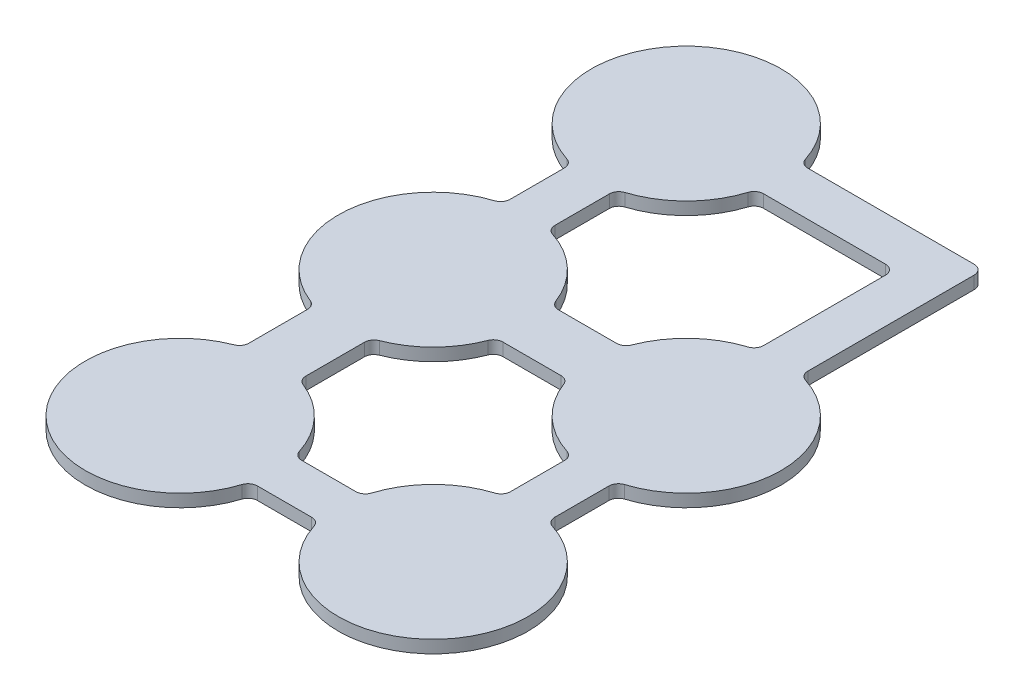
SolidWorks part; units mm, degrees
ref_plane "Front Plane" through (0, 0, 0) normal (0, 0, 1) x (1, 0, 0)
ref_plane "Top Plane" through (0, 0, 0) normal (0, 1, 0) x (1, 0, 0)
ref_plane "Right Plane" through (0, 0, 0) normal (1, 0, 0) x (0, 0, -1)
sketch "Sketch1" plane through (0, 0, 0) normal (0, 1, 0) x (1, 0, 0)
  line L0 (-10, 0) -> (10, 0) construction
  line L1 (-10, 0) -> (-10, 20) construction
  line L2 (-10, 0) -> (-10, -20) construction
  line L3 (-10, -20) -> (10, -20) construction
  line L4 (10, -20) -> (10, 0) construction
  line L6 (-11.775, 12.7131) -> (-8.225, 12.7131)
  line L7 (-11.775, 12.7131) -> (-11.775, 7.2869)
  line L8 (-11.775, 7.2869) -> (-8.225, 7.2869)
  line L9 (-8.225, 12.7131) -> (-8.225, 7.2869)
  line L14 (-12.25, -7.1545) -> (-7.75, -7.1545)
  line L15 (-12.25, -7.1545) -> (-12.25, -12.8455)
  line L16 (-12.25, -12.8455) -> (-7.75, -12.8455)
  line L17 (-7.75, -7.1545) -> (-7.75, -12.8455)
  line L18 (-2.707, -18.25) -> (2.707, -18.25)
  line L19 (-2.707, -18.25) -> (-2.707, -21.75)
  line L20 (-2.707, -21.75) -> (2.707, -21.75)
  line L21 (2.707, -18.25) -> (2.707, -21.75)
  line L22 (8.25, -7.293) -> (11.75, -7.293)
  line L23 (8.25, -7.293) -> (8.25, -12.707)
  line L24 (8.25, -12.707) -> (11.75, -12.707)
  line L25 (11.75, -7.293) -> (11.75, -12.707)
  line L26 (-2.8299, 2.2) -> (2.8299, 2.2)
  line L27 (-2.8299, 2.2) -> (-2.8299, -2.2)
  line L28 (-2.8299, -2.2) -> (2.8299, -2.2)
  line L29 (2.8299, 2.2) -> (2.8299, -2.2)
  line L30 (-2.707, 21.75) -> (11.75, 21.75)
  line L31 (-2.707, 21.75) -> (-2.707, 18.25)
  line L32 (-2.707, 18.25) -> (11.75, 18.25)
  line L33 (11.75, 21.75) -> (11.75, 18.25)
  line L34 (11.75, 7.293) -> (8.25, 7.293)
  line L35 (11.75, 7.293) -> (11.75, 21.75)
  line L36 (11.75, 21.75) -> (8.25, 21.75)
  line L37 (8.25, 7.293) -> (8.25, 21.75)
  circle A0 centre (10, 0) radius 7.5
  circle A1 centre (-10, 0) radius 7.5
  circle A2 centre (-10, 20) radius 7.5
  circle A3 centre (-10, -20) radius 7.5
  circle A4 centre (10, -20) radius 7.5
  point P10 (0, 0)
  point P15 (-10, 12.7131)
  point P33 (-10, -7.1545)
  point P34 (-2.707, -20)
  point P35 (10, -7.293)
  point P36 (-2.8299, 0)
  point P44 (6.0643, 7.5)
  point P45 (0, 0)
  point P46 (0, 0)
  point P47 (0, 0)
  point P48 (0, 0)
  point P49 (0, 0)
  dimension "D1" = 15
  dimension "D2" = 20
  dimension "D3" = 3.55
  dimension "D4" = 4.5
  dimension "D5" = 4.4
  dimension "D6" = 3.5
  dimension "D7" = 3.5
  dimension "D8" = 3.5
extrude "Boss-Extrude1" add sketch "Sketch1" along normal blind 1 contours A3 L17 A1 L15 | A4 L18 A3 L20 | A4 L25 A0 L23 | A0 L35 L32 L37 | A1 L28 A0 L26 | L37 L32 L33 L30 | A2 L32 L37 L30 | A2 L7 A1 L9 | A1 | A3 | A4 | A0 | A2 region at (-10, 0, -10) region at (2.8405, 0, -20) region at (-10, 0, 10) region at (10, 0, -20) region at (0, 0, 0) region at (10, 0, -12.8405) region at (0, 0, 20) region at (10, 0, 10)
fillet "Fillet1" radius 0.75 26 edges at (2.8299, 0.5, -2.2) (-2.8299, 0.5, -2.2) (11.75, 0.5, -21.75) (-2.707, 0.5, -21.75) (8.25, 0.5, -7.293) (11.75, 0.5, -7.293) (11.75, 0.5, 12.707) (2.707, 0.5, 21.75) (-2.707, 0.5, 21.75) (-2.707, 0.5, 18.25) (2.707, 0.5, 18.25) (8.25, 0.5, 12.707) (11.75, 0.5, 7.293) (-2.8299, 0.5, 2.2) (2.8299, 0.5, 2.2) (8.25, 0.5, 7.293) (-12.25, 0.5, 12.8455) (-7.75, 0.5, 12.8455) (-7.75, 0.5, 7.1545) (-12.25, 0.5, 7.1545) (-11.775, 0.5, -7.2869) (-8.225, 0.5, -7.2869) (8.25, 0.5, -18.25) (-2.707, 0.5, -18.25) (-8.225, 0.5, -12.7131) (-11.775, 0.5, -12.7131)
